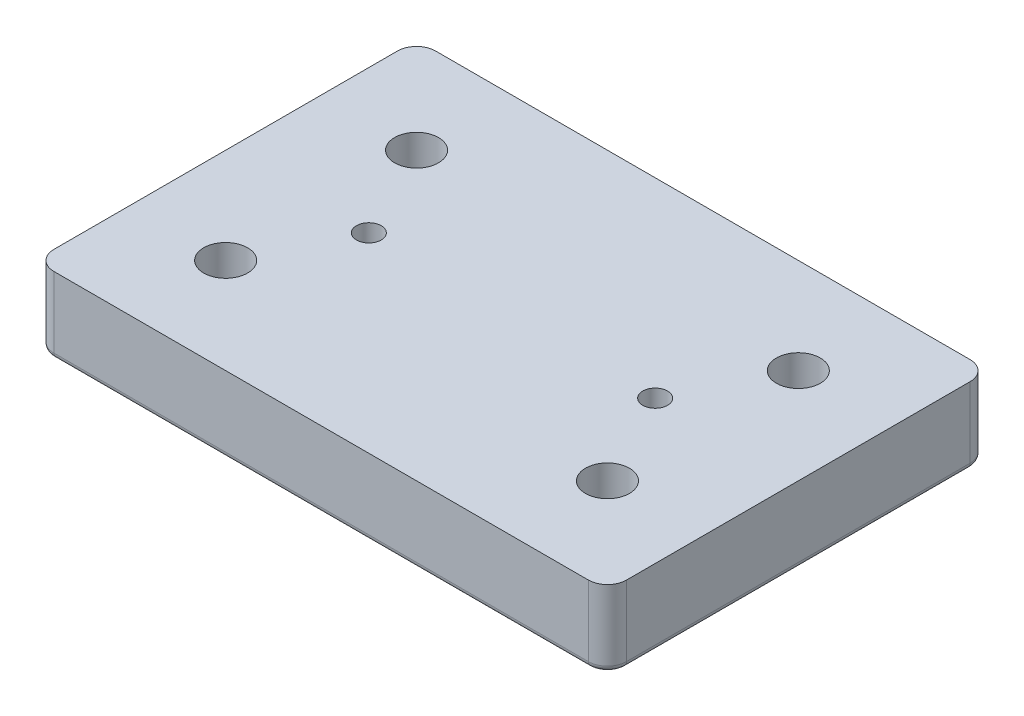
SolidWorks part; units mm, degrees
ref_plane "Front Plane" through (0, 0, 0) normal (0, 0, 1) x (1, 0, 0)
ref_plane "Top Plane" through (0, 0, 0) normal (0, 1, 0) x (1, 0, 0)
ref_plane "Right Plane" through (0, 0, 0) normal (1, 0, 0) x (0, 0, -1)
sketch "Sketch3" plane through (0, 0, 0) normal (0, 1, 0) x (1, 0, 0)
  line L0 (0, 0) -> (15, 0) construction
  line L1 (-15, -10) -> (15, -10)
  line L2 (-15, -10) -> (-15, 10)
  line L3 (-15, 10) -> (15, 10)
  line L4 (15, -10) -> (15, 10)
  line L5 (-15, -10) -> (15, 10) construction
  line L6 (-15, 10) -> (15, -10) construction
  line L7 (0, 0) -> (0, -4.3969) construction
  circle A0 centre (7.5, 0) radius 0.65
  circle A1 centre (-7.5, 0) radius 0.65
  point P0 (0, 0)
  dimension "D3" = 1.3
  dimension "D1" = 30
  dimension "D2" = 20
extrude "Boss-Extrude5" add sketch "Sketch3" along normal blind 4
sketch "Sketch6" plane through (0, 4, 0) normal (0, 1, 0) x (1, 0, 0)
  line L0 (-10, 5) -> (-10, -5)
  line L1 (-15, 10) -> (15, 10)
  line L2 (-15, 10) -> (-15, -10)
  line L3 (-15, -10) -> (15, -10)
  line L4 (15, 10) -> (15, -10)
  line L5 (-10, -5) -> (10, -5)
  line L6 (10, 5) -> (10, -5)
  line L7 (-10, 5) -> (10, 5)
  line L8 (0, 0) -> (0, 9.2986) construction
  line L9 (-0.1913, 0) -> (14.3497, 0) construction
  circle A0 centre (-10, 5) radius 1.15
  circle A1 centre (10, 5) radius 1.15
  circle A2 centre (10, -5) radius 1.15
  circle A3 centre (-10, -5) radius 1.15
  dimension "D2" = 2.3
  dimension "D1" = 5
extrude "Cut-Extrude1" cut sketch "Sketch6" against normal blind 2 contours L7 A0 L0 | L0 A0 L7 | A1 L7 L6 | A1 L6 L7 | L5 A2 L6 | L6 A2 L5 | A3 L5 L0 | A3 L0 L5 region at (-9.5119, 4, -4.5119) region at (-10.1627, 4, -5.1627) region at (-9.5119, 4, 4.5119) region at (-10.1627, 4, 5.1627) region at (10.1627, 4, -5.1627) region at (9.5119, 4, -4.5119) region at (9.5119, 4, 4.5119) region at (10.1627, 4, 5.1627)
fillet "Fillet1" radius 0.3 4 edges at (15, 0, 0) (0, 0, -10) (-15, 0, 0) (0, 0, 10)
fillet "Fillet2" radius 1 4 edges at (14.9121, 0.0879, 9.9121) (14.9121, 0.0879, -9.9121) (15, 2.15, -10) (15, 2.15, 10)
sketch "Sketch10" plane through (0, 2, 0) normal (0, 1, 0) x (1, 0, 0)
  circle A0 centre (10, -5) radius 1.15
  circle A1 centre (-7.5, 0) radius 0.65
  circle A2 centre (-10, 5) radius 1.15
  circle A3 centre (7.5, 0) radius 0.65
  circle A4 centre (10, 5) radius 1.15
  circle A5 centre (-10, -5) radius 1.15
extrude "Cut-Extrude3" cut sketch "Sketch10" against normal blind 10
fillet "Fillet3" radius 1 4 edges at (-14.9121, 0.0879, 9.9121) (-14.9121, 0.0879, -9.9121) (-15, 2.15, -10) (-15, 2.15, 10)
